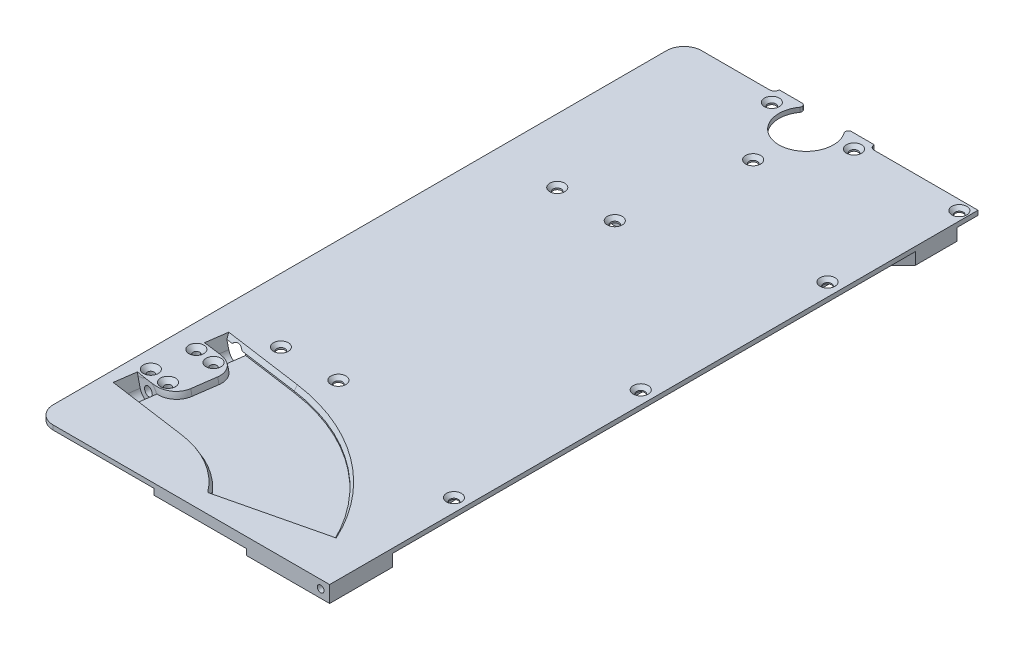
SolidWorks part; units mm, degrees
ref_plane "Front Plane" through (0, 0, 0) normal (0, 0, 1) x (1, 0, 0)
ref_plane "Top Plane" through (0, 0, 0) normal (0, 1, 0) x (1, 0, 0)
ref_plane "Right Plane" through (0, 0, 0) normal (1, 0, 0) x (0, 0, -1)
sketch "Sketch1" plane through (0, 0, 0) normal (0, 1, 0) x (1, 0, 0)
  line L0 (40, 88.1) -> (-40, -88.1) construction
  line L1 (-40, 88.1) -> (40, 88.1) construction
  line L2 (-40, 88.1) -> (-40, -88.1) construction
  line L3 (-40, -88.1) -> (40, -88.1) construction
  line L4 (40, 88.1) -> (40, -88.1) construction
  line L5 (40, 86.8) -> (-34, 86.8)
  line L6 (40, 86.8) -> (40, -86.8)
  line L7 (40, -86.8) -> (-34, -86.8)
  line L8 (-38.7, 82.1) -> (-38.7, -82.1)
  arc A0 (-34, 86.8) -> (-38.7, 82.1) centre (-34, 82.1) ccw
  arc A1 (-34, -86.8) -> (-38.7, -82.1) centre (-34, -82.1) cw
  dimension "D2" = 176.2
  dimension "D3" = 1.3
  dimension "D4" = 1.3
  dimension "D5" = 6
  dimension "D6" = 1.3
extrude "Boss-Extrude1" add sketch "Sketch1" against normal blind 1.2
sketch "Sketch4" plane through (0, -1.2, 0) normal (0, -1, 0) x (-1, 0, 0)
  line L0 (-40, -86.8) -> (-40, 86.8) construction
  line L1 (-40, -76.8) -> (22.7, -76.8)
  line L2 (-40, -76.8) -> (-40, 81.2)
  line L3 (-40, 81.2) -> (22.7, 81.2)
  line L4 (22.7, -76.8) -> (22.7, 81.2)
  line L7 (40, 88.1) -> (40, -88.1) construction
  line L8 (40, 88.1) -> (-40, 88.1) construction
  dimension "D1" = 158
  dimension "D3" = 17.3
  dimension "D2" = 6.9
extrude "Boss-Extrude3" add sketch "Sketch4" along normal blind 3.2
sketch "Sketch6" plane through (0, -1.2, 0) normal (0, -1, 0) x (1, 0, 0)
  line L0 (-40, -88.1) -> (-40, 88.1) construction
  line L1 (-22.8, -76.4) -> (-36.3, -76.4)
  line L2 (-22.8, -76.4) -> (-22.8, -64.75)
  line L3 (-22.8, -64.75) -> (-36.3, -64.75)
  line L4 (-36.3, -76.4) -> (-36.3, -64.75)
  line L5 (-22.8, 70.65) -> (-36.3, 70.65)
  line L6 (-22.8, 70.65) -> (-22.8, 41.45)
  line L7 (-22.8, 41.45) -> (-36.3, 41.45)
  line L8 (-36.3, 70.65) -> (-36.3, 41.45)
  line L9 (-40, -88.1) -> (40, -88.1) construction
  line L10 (-25.5, 56.05) -> (-22.8, 56.05) construction
  line L11 (-22.7, 76.8) -> (-22.7, -81.2) construction
  circle A0 centre (-25.5, -68.35) radius 1.1
  circle A1 centre (-25.5, 56.05) radius 1.1
  dimension "D7" = 2.2
  dimension "D1" = 3.7
  dimension "D2" = 29.2
  dimension "D3" = 17.2
  dimension "D4" = 124.4
  dimension "D5" = 19.75
  dimension "D6" = 2.8
  dimension "D8" = 2.8
  dimension "D9" = 3.6
  dimension "D10" = 5.7
extrude "Boss-Extrude4" add sketch "Sketch6" along normal blind 5.1
sketch "Sketch7" plane through (0, -1.2, 0) normal (0, -1, 0) x (1, 0, 0)
  line L0 (-22.7, 76.8) -> (-22.7, -81.2) construction
  line L1 (-22.8, -76.4) -> (-22.7, -76.4)
  line L2 (-22.8, -76.4) -> (-22.8, -64.75)
  line L3 (-22.8, -64.75) -> (-22.7, -64.75)
  line L4 (-22.7, -76.4) -> (-22.7, -64.75)
  line L5 (-22.8, -64.75) -> (-36.3, -64.75) construction
  line L6 (-22.7, 76.8) -> (-22.7, -81.2) construction
  line L7 (-22.8, 70.65) -> (-22.7, 70.65)
  line L8 (-22.8, 70.65) -> (-22.8, 41.45)
  line L9 (-22.8, 41.45) -> (-22.7, 41.45)
  line L10 (-22.7, 70.65) -> (-22.7, 41.45)
  line L11 (-36.3, 41.45) -> (-22.8, 41.45) construction
extrude "Boss-Extrude5" add sketch "Sketch7" along normal up to surface (3.2 mm away) up to face at (8.65, -4.4, -2.2)
sketch "Sketch9" plane through (0, 0, 0) normal (0, 1, 0) x (1, 0, 0)
  line L0 (-25.9598, -43.3304) -> (-31.3073, -42.5789) construction
  line L1 (-31.3073, -42.5789) -> (-34.9258, -68.3259) construction
  line L2 (-34.9258, -68.3259) -> (-29.5783, -69.0774) construction
  line L3 (-29.5783, -69.0774) -> (-25.9598, -43.3304) construction
  line L4 (-22.8, -70.65) -> (-36.3, -70.65) construction
  line L8 (-36.3, -70.65) -> (-36.3, -41.45) construction
  line L9 (-34.9258, -68.3259) -> (-34.2299, -63.3745)
  line L10 (-34.9258, -68.3259) -> (-29.5783, -69.0774)
  line L11 (-34.2299, -63.3745) -> (-28.8825, -64.1261)
  line L12 (-29.5783, -69.0774) -> (-28.8825, -64.1261)
  line L13 (-25.9598, -43.3304) -> (-31.3073, -42.5789)
  line L14 (-25.9598, -43.3304) -> (-26.6557, -48.2818)
  line L15 (-31.3073, -42.5789) -> (-32.0032, -47.5303)
  line L16 (-26.6557, -48.2818) -> (-32.0032, -47.5303)
  line L17 (-29.5783, -69.0774) -> (-22.6165, -70.0558) construction
  line L18 (-22.6165, -70.0558) -> (-22.7, -70.65) construction
  dimension "D1" = 5.4
  dimension "D3" = 8
  dimension "D2" = 26
  dimension "D4" = 1.3742
  dimension "D5" = 5
  dimension "D6" = 0.6
sketch "Sketch10" plane through (0, -6.3, 0) normal (0, -1, 0) x (1, 0, 0)
  line L0 (-25.9598, 43.3304) -> (-25.6956, 41.45)
  line L1 (-36.3, 41.45) -> (-22.8, 41.45) construction
  line L2 (-25.9598, 43.3304) -> (-39.3399, 41.45)
  line L3 (-36.3, 41.45) -> (-22.7, 41.45) construction
  line L4 (-25.9598, 43.3304) -> (-31.3073, 42.5789) construction
  line L5 (-25.9598, 43.3304) -> (-26.6557, 48.2818) construction
  line L6 (-39.3399, 41.45) -> (-25.6956, 41.45)
  line L7 (-29.5783, 69.0774) -> (-29.7994, 70.65)
  line L8 (-22.7, 70.65) -> (-36.3, 70.65) construction
  line L9 (-29.7994, 70.65) -> (-36.3, 70.65)
  line L10 (-36.3, 70.65) -> (-36.3, 68.1327)
  line L11 (-36.3, 70.65) -> (-36.3, 41.45) construction
  line L12 (-36.3, 68.1327) -> (-29.5783, 69.0774)
  line L13 (-29.5783, 69.0774) -> (-28.8825, 64.1261) construction
  line L14 (-36.3, 70.65) -> (-36.3, 41.45) construction
extrude "Cut-Extrude5" cut sketch "Sketch10" against normal up to surface (5.1 mm away) up to face at (-14.9304, -1.2, -3.7167)
extrude "Cut-Extrude6" cut sketch "Sketch9" against normal blind 5.2
sketch "Sketch11" plane through (-9.3972, 0, 66.8646) normal (-0.1392, 0, 0.9903) x (0.9903, 0, 0.1392)
  line L0 (-19.6768, 0) -> (-25.0768, 0) construction
  line L1 (-22.3768, -2.5) -> (-22.3768, 0) construction
  circle A0 centre (-22.3768, -2.5) radius 1.2
  dimension "D1" = 2.4
  dimension "D2" = 2.5
extrude "Cut-Extrude7" cut sketch "Sketch11" against normal blind 5.4
sketch "Sketch15" plane through (-9.3972, 0, 66.8646) normal (-0.1392, 0, 0.9903) x (0.9903, 0, 0.1392)
  line L0 (-22.3768, -2.5) -> (-24.9722, -3.2442) construction
  line L1 (-19.6768, -5.2) -> (-25.0768, -5.2) construction
  line L2 (-24.9722, -3.2442) -> (-25.9024, 0) construction
  line L3 (-21.5889, 0) -> (-26.8973, 0) construction
  line L4 (-25.9024, 0) -> (-25.0768, 0)
  line L5 (-25.0768, -5.2) -> (-25.0768, 0) construction
  line L6 (-25.0768, 0) -> (-25.0768, -2.8795)
  line L7 (-25.0768, -2.8795) -> (-25.9024, 0)
  circle A0 centre (-22.3768, -2.5) radius 1.2 construction
  dimension "D1" = 16
  dimension "D2" = 2.7
extrude "Cut-Extrude8" cut sketch "Sketch15" along normal up to surface (5 mm away) up to face at (-32.2521, -0.6, 68.7016)
sketch "Sketch17" plane through (-9.3972, 0, 66.8646) normal (-0.1392, 0, 0.9903) x (0.9903, 0, 0.1392)
  line L0 (-25.0768, -2.8795) -> (-24.9722, -3.2442)
  line L1 (-25.9024, 0) -> (-25.0768, -2.8795) construction
  line L2 (-19.6768, -1.2) -> (-19.6768, -6.3) construction
  line L3 (-19.6768, -2.5) -> (-19.6768, -6.3)
  line L4 (-19.6768, -6.3) -> (-25.0768, -6.3)
  line L5 (-25.0768, -6.3) -> (-25.0768, -2.8795)
  line L6 (-26.4645, -6.3) -> (-19.6768, -6.3) construction
  arc A0 (-19.6768, -2.5) -> (-24.9722, -3.2442) centre (-22.3768, -2.5) cw
extrude "Boss-Extrude6" add sketch "Sketch17" along normal up to surface (5 mm away) up to face at (-33.8587, -4.0399, 68.4758)
sketch "Sketch18" plane through (-7.1704, 0, 51.0203) normal (0.1392, 0, -0.9903) x (-0.9903, 0, -0.1392)
  line L3 (25.9024, 0) -> (25.0768, 0)
  line L4 (25.0768, 0) -> (25.0768, -2.8795)
  line L5 (25.0768, -2.8795) -> (25.9024, 0)
  line L6 (25.9024, 0) -> (25.0768, 0)
  line L7 (25.0768, 0) -> (25.0768, -2.8795)
  line L8 (25.0768, -2.8795) -> (25.9024, 0)
  dimension "D1" = 0
extrude "Cut-Extrude9" cut sketch "Sketch18" along normal up to surface (5 mm away) up to face at (-28.6336, -0.6, 42.9547)
sketch "Sketch19" plane through (-7.1704, 0, 51.0203) normal (0.1392, 0, -0.9903) x (-0.9903, 0, -0.1392)
  line L4 (25.0768, -2.8795) -> (24.9722, -3.2442)
  line L5 (19.6768, -2.5) -> (19.6768, -6.3)
  line L6 (19.6768, -6.3) -> (25.0768, -6.3)
  line L7 (25.0768, -6.3) -> (25.0768, -2.8795)
  line L8 (25.0768, -2.8795) -> (24.9722, -3.2442)
  line L9 (19.6768, -2.5) -> (19.6768, -6.3)
  line L10 (19.6768, -6.3) -> (25.0768, -6.3)
  line L11 (25.0768, -6.3) -> (25.0768, -2.8795)
  arc A1 (19.6768, -2.5) -> (24.9722, -3.2442) centre (22.3768, -2.5) ccw
  arc A2 (19.6768, -2.5) -> (24.9722, -3.2442) centre (22.3768, -2.5) ccw
  dimension "D1" = 0
extrude "Boss-Extrude7" add sketch "Sketch19" along normal up to surface (5 mm away) up to face at (-31.2741, -4.0399, 42.5836)
sketch "Sketch20" plane through (0, -6.3, 0) normal (0, -1, 0) x (1, 0, 0)
  line L0 (-36.3, 68.1327) -> (-36.3, 41.8772) construction
  line L1 (-36.3, 59.05) -> (-28.3, 59.05)
  line L2 (-36.3, 59.05) -> (-36.3, 53.05)
  line L3 (-36.3, 53.05) -> (-28.3, 53.05)
  line L4 (-28.3, 59.05) -> (-28.3, 53.05)
  line L5 (-25.5, 56.05) -> (-28.3, 56.05) construction
extrude "Cut-Extrude10" cut sketch "Sketch20" against normal blind 3.6
sketch "Sketch22" plane through (0, -2.7, 0) normal (0, -1, 0) x (-1, 0, 0)
  line L0 (28.3, -59.05) -> (36.3, -59.05) construction
  line L1 (24.0566, -58.55) -> (26.9434, -58.55)
  line L2 (26.9434, -58.55) -> (28.3868, -56.05) construction
  line L3 (28.3868, -56.05) -> (26.9434, -53.55) construction
  line L4 (26.9434, -53.55) -> (24.0566, -53.55)
  line L5 (24.0566, -53.55) -> (22.6132, -56.05)
  line L6 (22.6132, -56.05) -> (24.0566, -58.55)
  line L7 (26.9434, -58.55) -> (28.3, -58.55)
  line L8 (28.3, -53.05) -> (28.3, -59.05) construction
  line L9 (28.3, -58.55) -> (28.3, -53.55)
  line L10 (28.3, -53.55) -> (26.9434, -53.55)
  circle A0 centre (25.5, -56.05) radius 2.5 construction
  dimension "D1" = 5
extrude "Cut-Extrude12" cut sketch "Sketch22" along normal blind 1.8
ref_plane "Plane1" through (-7.1426, 0, 50.8222) normal (0.1392, 0, -0.9903) x (-0.9903, 0, -0.1392)
sketch "Sketch23" plane through (-7.1704, 0, 51.0203) normal (0.1392, 0, -0.9903) x (-0.9903, 0, -0.1392)
  circle A0 centre (22.3768, -2.5) radius 1.2
  dimension "D1" = 2.4
extrude "Cut-Extrude13" cut sketch "Sketch23" against normal blind 5.4
sketch "Sketch24" plane through (0, 0, 0) normal (0, 1, 0) x (1, 0, 0)
  line L0 (-32.365, -50.1049) -> (-27.0176, -50.8565) construction
  line L1 (-32.365, -50.1049) -> (-33.8681, -60.7998) construction
  line L2 (-27.0176, -50.8565) -> (-28.5206, -61.5514) construction
  line L3 (-33.8681, -60.7998) -> (-28.5206, -61.5514) construction
  line L5 (-32.1249, -42.464) -> (-32.8208, -47.4153) construction
  line L6 (-29.3294, -47.906) -> (-29.6913, -50.4807) construction
  line L7 (-32.8208, -47.4153) -> (-26.6557, -48.2818) construction
  line L8 (-28.8825, -64.1261) -> (-35.0476, -63.2596) construction
  line L9 (-28.1411, -48.073) -> (-30.5178, -47.739) construction
  circle A0 centre (-32.365, -50.1049) radius 2 construction
  circle A1 centre (-27.0176, -50.8565) radius 2 construction
  circle A2 centre (-28.5206, -61.5514) radius 2 construction
  circle A3 centre (-33.8681, -60.7998) radius 2 construction
  circle A4 centre (-32.365, -50.1049) radius 0.9
  circle A5 centre (-27.0176, -50.8565) radius 0.9
  circle A6 centre (-28.5206, -61.5514) radius 0.9
  circle A7 centre (-33.8681, -60.7998) radius 0.9
  dimension "D1" = 4
  dimension "D2" = 1.8
  dimension "D3" = 5.4
  dimension "D4" = 2.6
  dimension "D5" = 2.6
extrude "Cut-Extrude14" cut sketch "Sketch24" against normal through all
chamfer "Chamfer1" distance 1.1 angle 45 4 edges at (-33.8681, 0, 61.6998) (-28.5206, 0, 62.4514) (-32.365, 0, 51.0049) (-27.0176, 0, 51.7565)
sketch "Sketch26" plane through (-6.4746, 0, 46.0689) normal (0.1392, 0, -0.9903) x (-0.9903, 0, -0.1392)
  circle A0 centre (22.3768, -2.5) radius 2
  circle A1 centre (22.3768, -2.5) radius 1.2 construction
  dimension "D1" = 4
extrude "Cut-Extrude15" cut sketch "Sketch26" along normal blind 12
sketch "Sketch27" plane through (-10.0931, 0, 71.8159) normal (-0.1392, 0, 0.9903) x (0.9903, 0, 0.1392)
  circle A0 centre (-22.3768, -2.5) radius 2
  dimension "D1" = 4
extrude "Cut-Extrude16" cut sketch "Sketch27" along normal blind 12
sketch "Sketch28" plane through (0, -6.3, 0) normal (0, -1, 0) x (1, 0, 0)
  line L1 (-28.3868, -68.35) -> (-26.9434, -70.85) construction
  line L2 (-26.9434, -70.85) -> (-24.0566, -70.85)
  line L3 (-24.0566, -70.85) -> (-22.6132, -68.35)
  line L4 (-22.6132, -68.35) -> (-24.0566, -65.85)
  line L5 (-24.0566, -65.85) -> (-26.9434, -65.85)
  line L6 (-26.9434, -65.85) -> (-28.3868, -68.35) construction
  line L8 (-22.8, -64.75) -> (-36.3, -64.75) construction
  line L10 (-26.9434, -70.85) -> (-35.1868, -70.85)
  line L11 (-35.1868, -70.85) -> (-35.1868, -64.75)
  line L12 (-35.1868, -64.75) -> (-28.3868, -64.75)
  line L14 (-28.3868, -64.75) -> (-28.3868, -65.85)
  line L15 (-28.3868, -65.85) -> (-26.9434, -65.85)
  circle A0 centre (-25.5, -68.35) radius 2.5 construction
  circle A1 centre (-25.5, -68.35) radius 1.1 construction
  dimension "D1" = 5
  dimension "D2" = 6.8
extrude "Cut-Extrude17" cut sketch "Sketch28" along normal blind 1.8 from surface at -3.6 starting at face at (-29.4232, -2.7, 55.9978)
sketch "Sketch29" plane through (0, -6.3, 0) normal (0, -1, 0) x (1, 0, 0)
  line L0 (-22.8, -64.75) -> (-36.3, -64.75) construction
  line L1 (-35.1868, -70.85) -> (-28.3868, -70.85)
  line L2 (-35.1868, -70.85) -> (-35.1868, -64.75)
  line L3 (-35.1868, -64.75) -> (-28.3868, -64.75)
  line L4 (-28.3868, -70.85) -> (-28.3868, -64.75)
extrude "Cut-Extrude18" cut sketch "Sketch29" against normal up to next
sketch "Sketch31" plane through (0, -4.4, 0) normal (0, -1, 0) x (1, 0, 0)
  line L0 (40, 70) -> (32.8, 62.8)
  line L1 (40, -81.2) -> (40, 76.8) construction
  line L2 (32.8, 62.8) -> (32.8, -62.8)
  line L3 (32.8, -62.8) -> (40, -70)
  line L4 (40, -70) -> (40, 70)
  line L5 (40, -88.1) -> (40, 88.1) construction
  point P8 (40, 0)
  dimension "D1" = 140
  dimension "D2" = 45
  dimension "D3" = 45
  dimension "D4" = 7.2
extrude "Cut-Extrude19" cut sketch "Sketch31" against normal up to surface (3.2 mm away) up to face at (-25.5, -1.2, 54.95)
sketch "Sketch32" plane through (0, 0, 0) normal (0, 1, 0) x (1, 0, 0)
  line L0 (36.5, 50) -> (36.5, 0) construction
  line L1 (36.5, 0) -> (36.5, -50) construction
  line L2 (40, 86.8) -> (40, -86.8) construction
  line L3 (36.5, 0) -> (40, 0) construction
  line L5 (40, -70) -> (40, 70) construction
  circle A0 centre (36.5, 50) radius 1.1
  circle A1 centre (36.5, 0) radius 1.1
  circle A2 centre (36.5, -50) radius 1.1
  dimension "D1" = 2.2
  dimension "D2" = 50
  dimension "D3" = 3.5
extrude "Cut-Extrude20" cut sketch "Sketch32" against normal up to next
chamfer "Chamfer2" distance 0.9 angle 45 3 edges at (36.5, 0, 51.1) (36.5, 0, 1.1) (36.5, 0, -48.9)
sketch "Sketch33" plane through (0, 0, 0) normal (0, 1, 0) x (1, 0, 0)
  line L0 (-28.6614, -43.1527) -> (-10.8019, -45.6627) construction
  line L1 (-28.6614, -43.1527) -> (-29.3016, -47.708) construction
  line L2 (-29.3016, -47.708) -> (-26.8259, -48.0559) construction
  line L3 (-22.5704, -53.7031) -> (-23.4612, -60.0408) construction
  line L4 (-29.1084, -64.2963) -> (-31.584, -63.9484) construction
  line L5 (-31.584, -63.9484) -> (-32.2242, -68.5036) construction
  line L6 (-32.2242, -68.5036) -> (-14.3647, -71.0136) construction
  line L7 (-25.9598, -43.3304) -> (-26.6557, -48.2818) construction
  line L8 (-28.1411, -48.073) -> (-30.5178, -47.739) construction
  line L9 (-32.8208, -47.4153) -> (-26.6557, -48.2818) construction
  line L10 (28.8162, -74.5036) -> (2.6914, -80.7659) construction
  line L11 (2.6914, -80.7659) -> (9.7561, -89.6538) construction
  line L14 (28.8162, -74.5036) -> (9.7561, -89.6538) construction
  line L15 (-29.0805, -64.0982) -> (-31.7543, -63.7225)
  line L16 (-31.7543, -63.7225) -> (-32.4501, -68.6738)
  line L17 (-32.4501, -68.6738) -> (-14.3926, -71.2116)
  line L18 (29.1042, -74.6402) -> (2.6138, -80.9902)
  line L19 (-28.8316, -42.9268) -> (-10.7741, -45.4647)
  line L20 (-28.8316, -42.9268) -> (-29.5275, -47.8782)
  line L21 (-29.5275, -47.8782) -> (-26.8538, -48.254)
  line L22 (-22.7685, -53.6753) -> (-23.6592, -60.013)
  arc A0 (-26.8259, -48.0559) -> (-22.5704, -53.7031) centre (-27.5218, -53.0072) cw construction
  arc A1 (-23.4612, -60.0408) -> (-29.1084, -64.2963) centre (-28.4125, -59.345) cw construction
  arc A2 (-14.3647, -71.0136) -> (2.6914, -80.7659) centre (-18.0527, -97.2547) cw construction
  arc A3 (-10.8019, -45.6627) -> (28.8162, -74.5036) centre (-18.0527, -97.2547) cw construction
  arc A4 (-14.3926, -71.2116) -> (2.6138, -80.9902) centre (-18.0527, -97.2547) cw
  arc A5 (-10.7741, -45.4647) -> (29.1042, -74.6402) centre (-18.0527, -97.2547) cw
  arc A6 (-26.8538, -48.254) -> (-22.7685, -53.6753) centre (-27.5218, -53.0072) cw
  arc A7 (-23.6592, -60.013) -> (-29.0805, -64.0982) centre (-28.4125, -59.345) cw
  point P17 (-29.3294, -47.906)
  dimension "D2" = 2.5
  dimension "D3" = 5
  dimension "D7" = 26.499
  dimension "D1" = 4.6
  dimension "D4" = 16.4
  dimension "D5" = 0.2
  dimension "D6" = 18.035
  dimension "D8" = 65
  dimension "D9" = 21.48
sketch "Sketch34" plane through (0, -1.2, 0) normal (0, -1, 0) x (-1, 0, 0)
  line L0 (-40, -76.8) -> (22.7, -76.8) construction
  line L1 (-40, -86.8) -> (7.06, -86.8)
  line L2 (-40, -86.8) -> (-40, -76.8)
  line L3 (-40, -76.8) -> (7.06, -76.8)
  line L4 (7.06, -86.8) -> (7.06, -76.8)
  line L6 (40, 88.1) -> (-40, 88.1) construction
  line L7 (7.16, -76.8) -> (16.16, -67.8) construction
  line L8 (16.16, -67.8) -> (16.16, 88.1) construction
  line L9 (40, 88.1) -> (40, -88.1) construction
  line L10 (40, -88.1) -> (-40, -88.1) construction
  dimension "D2" = 23.84
  dimension "D3" = 11.3
  dimension "D1" = 135
  dimension "D4" = 9
extrude "Boss-Extrude8" add sketch "Sketch34" along normal blind 1.6
sketch "Sketch35" plane through (0, -2.8, 0) normal (0, -1, 0) x (1, 0, 0)
  line L0 (40, 76.8) -> (-22.7, 76.8) construction
  line L1 (40, 86.8) -> (17.8, 86.8)
  line L2 (40, 86.8) -> (40, 76.8)
  line L3 (40, 76.8) -> (17.8, 76.8)
  line L4 (17.8, 86.8) -> (17.8, 76.8)
  line L5 (-40, -88.1) -> (-40, 88.1) construction
  dimension "D1" = 57.8
extrude "Boss-Extrude9" add sketch "Sketch35" along normal up to surface (1.6 mm away) up to face at (-6.283, -4.4, -4.7182)
extrude "Cut-Extrude21" cut sketch "Sketch33" against normal blind 1.6
sketch "Sketch37" plane through (-9.3972, 0, 66.8646) normal (-0.1392, 0, 0.9903) x (0.9903, 0, 0.1392)
  line L5 (-21.4768, 0) -> (-19.8768, 0) construction
  line L6 (-19.8768, 0) -> (-19.8768, -1.6)
  line L7 (-19.8768, 0) -> (-25.9024, 0) construction
  line L8 (-21.4768, 0) -> (-21.4768, 1)
  line L9 (-21.4768, 1) -> (-19.8768, 1)
  line L10 (-19.8768, 1) -> (-19.8768, 0)
  arc A1 (-21.4768, 0) -> (-19.8768, -1.6) centre (-22.3768, -2.5) cw
  circle A2 centre (-22.3768, -2.5) radius 1.2 construction
  dimension "D1" = 1
sketch "Sketch44" plane through (0, 0, 86.8) normal (0, 0, 1) x (1, 0, 0)
  line L0 (40, -4.4) -> (40, 0) construction
  line L1 (17.8, -4.4) -> (40, -4.4) construction
  circle A0 centre (37.6, -2.2) radius 0.9
  dimension "D1" = 1.8
extrude "Cut-Extrude22" cut sketch "Sketch44" against normal blind 9
sketch "Sketch45" plane through (0, 0, 0) normal (0, 1, 0) x (1, 0, 0)
  line L0 (-40, 88.1) -> (40, 88.1) construction
  line L1 (40, 86.8) -> (40, -86.8) construction
  circle A0 centre (37.6, 84.2) radius 1.1
  dimension "D3" = 2.2
  dimension "D1" = 3.9
extrude "Cut-Extrude23" cut sketch "Sketch45" against normal up to next
chamfer "Chamfer3" distance 0.9 angle 45 1 edges at (37.6, 0, -83.1)
sketch "Sketch50" plane through (-9.3972, 0, 66.8646) normal (-0.1392, 0, 0.9903) x (0.9903, 0, 0.1392)
  line L5 (-23.931, -0.3449) -> (-25.469, -0.7859)
  line L6 (-25.9024, 0) -> (-24.9722, -3.2442) construction
  arc A2 (-19.8768, -1.6) -> (-23.931, -0.3449) centre (-22.3768, -2.5) ccw
  circle A3 centre (-22.3768, -2.5) radius 1.2 construction
  arc A4 (-19.8768, 0) -> (-25.469, -0.7859) centre (-22.3768, -2.5) ccw
sketch "Sketch51" plane through (0, -1.6, 0) normal (0, 1, 0) x (1, 0, 0)
  line L0 (-29.0805, -64.0982) -> (-29.7764, -69.0496)
  line L1 (-29.7764, -69.0496) -> (-20.0718, -70.4135)
  line L2 (-20.0718, -70.4135) -> (-16.4533, -44.6665)
  line L3 (-16.4533, -44.6665) -> (-26.1579, -43.3026)
  line L4 (-26.1579, -43.3026) -> (-26.8538, -48.254)
  line L5 (-29.5783, -69.0774) -> (-28.8825, -64.1261) construction
  line L6 (-22.7685, -53.6753) -> (-23.6592, -60.013)
  line L7 (-29.0805, -64.0982) -> (-31.5562, -63.7503) construction
  arc A0 (-29.0805, -64.0982) -> (-23.6592, -60.013) centre (-28.4125, -59.345) ccw
  arc A1 (-26.8538, -48.254) -> (-22.7685, -53.6753) centre (-27.5218, -53.0072) cw
  dimension "D2" = 4.8
  dimension "D1" = 5
  dimension "D3" = 5
ref_plane "Plane3" through (-21.9881, -6.367, -3.0902) normal (0.9519, 0.2756, 0.1338) x (0.1285, 0.0372, -0.991)
sketch "Sketch54" plane through (-7.1704, 0, 51.0203) normal (0.1392, 0, -0.9903) x (-0.9903, 0, -0.1392)
  line L0 (24.9722, -3.2442) -> (25.9024, 0) construction
  arc A0 (19.8768, -1.6) -> (23.931, -0.3449) centre (22.3768, -2.5) cw
  dimension "D1" = 1.8
sketch "Sketch53" plane through (-21.9881, -6.367, -3.0902) normal (0.9519, 0.2756, 0.1338) x (0.1285, 0.0372, -0.991)
  line L0 (-67.2286, 8.8737) -> (-72.2248, 9.0673)
  line L2 (-72.2248, 9.0673) -> (-71.8455, 18.8599)
  line L3 (-71.8455, 18.8599) -> (-45.8649, 17.8535)
  line L4 (-45.8649, 17.8535) -> (-46.2443, 8.0608)
  line L6 (-46.2443, 8.0608) -> (-51.2406, 8.2544)
  line L7 (-62.2464, 13.4843) -> (-55.8511, 13.2366)
  line L8 (-67.3185, 6.5515) -> (-72.3148, 6.7451) construction
  line L11 (-46.3343, 5.7386) -> (-51.3305, 5.9322) construction
  line L12 (-67.2286, 8.8737) -> (-67.3065, 6.8613) construction
  arc A0 (-67.2286, 8.8737) -> (-62.2464, 13.4843) centre (-62.4322, 8.6879) cw
  arc A1 (-51.2406, 8.2544) -> (-55.8511, 13.2366) centre (-56.037, 8.4402) ccw
  dimension "D1" = 4.8
  dimension "D2" = 5
sweep "Cut-Sweep2" cut profiles "Sketch51" path "Sketch54"
extrude "Cut-Extrude24" cut sketch "Sketch53" against normal blind 1.8
chamfer "Chamfer4" distance 1.2 angle 30 5 edges at (-4.9435, 0, 74.4559) (15.859, 0, 77.8152) (12.8279, 0, 55.046)
sketch "Sketch55" plane through (0, -4.4, 0) normal (0, -1, 0) x (1, 0, 0)
  line L0 (-25.6956, 41.45) -> (-22.8, 41.45) construction
  line L1 (-3, 41.45) -> (-38.8, 41.45) construction
  line L2 (-3, 41.45) -> (-3, -38.95) construction
  line L3 (-3, -38.95) -> (-38.8, -38.95) construction
  line L4 (-38.8, 41.45) -> (-38.8, -38.95) construction
  line L6 (-3, 38.25) -> (-3, -35.75)
  line L7 (-6.2, -38.95) -> (-38.8, -38.95)
  line L8 (-38.8, -38.95) -> (-38.8, 41.45)
  line L9 (-38.8, 41.45) -> (-6.2, 41.45)
  line L11 (-40, -88.1) -> (-40, 88.1) construction
  arc A0 (-6.2, 41.45) -> (-3, 38.25) centre (-6.2, 38.25) cw
  arc A1 (-3, -35.75) -> (-6.2, -38.95) centre (-6.2, -35.75) cw
  dimension "D4" = 3.2
  dimension "D1" = 80.4
  dimension "D2" = 35.8
  dimension "D3" = 1.2
extrude "Cut-Extrude25" cut sketch "Sketch55" along direction (0, -1, 0) on the side against the normal offset from surface (4 mm away) 0.4
sketch "Sketch56" plane through (0, -0.4, 0) normal (0, -1, 0) x (1, 0, 0)
  line L0 (-3, 35.95) -> (-21.6, 35.95)
  line L1 (-3, -33.45) -> (-21.6, -33.45)
  line L2 (-3, 38.25) -> (-3, -35.75) construction
  line L3 (-23.9, -35.75) -> (-23.9, -38.95)
  line L4 (-6.2, -38.95) -> (-38.7, -38.95) construction
  line L5 (-21.6, -35.75) -> (-6.2, -35.75) construction
  line L6 (-3, -33.45) -> (-3, -35.75)
  line L7 (-6.2, -38.95) -> (-23.9, -38.95)
  line L8 (-23.9, 38.25) -> (-23.9, 41.45)
  line L9 (-38.7, 41.45) -> (-6.2, 41.45) construction
  line L10 (-23.9, 41.45) -> (-6.2, 41.45)
  line L11 (-3, 35.95) -> (-3, 38.25)
  arc A0 (-21.6, -33.45) -> (-23.9, -35.75) centre (-21.6, -35.75) ccw
  arc A1 (-21.6, 35.95) -> (-23.9, 38.25) centre (-21.6, 38.25) cw
  circle A2 centre (-21.6, -35.75) radius 1.1 construction
  circle A4 centre (-6.2, -35.75) radius 1.1 construction
  arc A5 (-6.2, -38.95) -> (-3, -35.75) centre (-6.2, -35.75) ccw construction
  arc A6 (-3, -35.75) -> (-6.2, -38.95) centre (-6.2, -35.75) cw
  arc A7 (-6.2, 41.45) -> (-3, 38.25) centre (-6.2, 38.25) cw
  dimension "D1" = 2.2
  dimension "D3" = 15.4
extrude "Boss-Extrude10" add sketch "Sketch56" along normal blind 0.9
sketch "Sketch57" plane through (0, -1.3, 0) normal (0, -1, 0) x (-1, 0, 0)
  circle A0 centre (21.6, 35.75) radius 1.1
  circle A1 centre (6.2, 35.75) radius 1.1
  circle A2 centre (6.2, -38.25) radius 1.1
  circle A3 centre (21.6, -38.25) radius 1.1
  arc A4 (23.9, -38.25) -> (21.6, -35.95) centre (21.6, -38.25) ccw construction
  arc A5 (3, -38.25) -> (6.2, -41.45) centre (6.2, -38.25) ccw construction
  arc A8 (6.2, 38.95) -> (3, 35.75) centre (6.2, 35.75) ccw construction
  arc A9 (21.6, 33.45) -> (23.9, 35.75) centre (21.6, 35.75) ccw construction
  dimension "D1" = 2.2
extrude "Cut-Extrude26" cut sketch "Sketch57" against normal up to surface (1.3 mm away) up to face at (37.6, 0, -86.2)
sketch "Sketch58" plane through (0, -1.3, 0) normal (0, -1, 0) x (1, 0, 0)
  line L0 (-22.7, -38.95) -> (-22.7, -37.7699)
  line L1 (-23.9, -35.75) -> (-23.9, -38.95)
  line L2 (-23.9, -35.75) -> (-23.9, -38.95) construction
  line L3 (-23.9, -38.95) -> (-22.7, -38.95)
  arc A0 (-23.9, -35.75) -> (-22.7, -37.7699) centre (-21.6, -35.75) ccw
  arc A1 (-21.6, -33.45) -> (-23.9, -35.75) centre (-21.6, -35.75) ccw construction
extrude "Cut-Extrude27" cut sketch "Sketch58" against normal up to surface (0.9 mm away) up to face at (-22.3153, -0.4, 1.25)
chamfer "Chamfer5" distance 0.9 angle 45 4 edges at (-21.6, 0, 37.15) (-6.2, 0, 37.15) (-6.2, 0, -36.85) (-21.6, 0, -36.85)
sketch "Sketch59" plane through (0, -4.4, 0) normal (0, -1, 0) x (1, 0, 0)
  line L0 (32.8, -62.8) -> (32.8, 62.8) construction
  line L1 (32.8, 33.8) -> (-3, 33.8)
  line L2 (32.8, 33.8) -> (32.8, 17.9)
  line L3 (32.8, 17.9) -> (-3, 17.9)
  line L4 (-3, 33.8) -> (-3, 17.9)
  line L5 (-3, 35.95) -> (-3, -33.45) construction
  line L6 (32.8, 25.85) -> (-3, 25.85) construction
  line L7 (-6.2, 41.45) -> (-22.8, 41.45) construction
  dimension "D1" = 15.6
  dimension "D2" = 15.9
extrude "Cut-Extrude28" cut sketch "Sketch59" against normal blind 0.4
sketch "Sketch60" plane through (0, -4, 0) normal (0, -1, 0) x (1, 0, 0)
  line L0 (-3, 17.9) -> (32.8, 17.9) construction
  line L1 (-3, 33.8) -> (-1.8, 33.8)
  line L2 (-3, 33.8) -> (-3, 17.9)
  line L3 (-3, 17.9) -> (-1.8, 17.9)
  line L4 (-1.8, 33.8) -> (-1.8, 17.9)
  dimension "D1" = 1.2
extrude "Cut-Extrude29" cut sketch "Sketch60" against normal up to surface (3.6 mm away) up to face at (-22.1955, -0.4, 1.0431)
fillet "Fillet1" radius 1.2 2 edges at (-1.8, -4, 25.85) (-1.8, -0.4, 25.85)
sketch "Sketch61" plane through (0, -4.4, 0) normal (0, -1, 0) x (1, 0, 0)
  line L0 (-40, -88.1) -> (-40, 88.1) construction
  line L1 (12.2, -65.4) -> (-15.8, -65.4) construction
  line L2 (12.2, -65.4) -> (12.2, -87.4) construction
  line L3 (12.2, -87.4) -> (-15.8, -87.4) construction
  line L4 (-15.8, -65.4) -> (-15.8, -87.4) construction
  line L5 (-40, -88.1) -> (40, -88.1) construction
  line L7 (-16, -86.8) -> (-16, -68.6)
  line L9 (-12.6, -65.2) -> (9, -65.2)
  line L10 (12.4, -68.6) -> (12.4, -86.8)
  line L11 (40, -86.8) -> (-34, -86.8) construction
  line L12 (-16, -86.8) -> (12.4, -86.8)
  arc A0 (-12.6, -65.2) -> (-16, -68.6) centre (-12.6, -68.6) ccw
  arc A1 (9, -65.2) -> (12.4, -68.6) centre (9, -68.6) cw
  dimension "D5" = 0.2
  dimension "D8" = 3.4
  dimension "D1" = 22
  dimension "D2" = 28
  dimension "D3" = 0.7
  dimension "D6" = 0.2
  dimension "D7" = 0.2
  dimension "D4" = 24
extrude "Cut-Extrude30" cut sketch "Sketch61" against normal up to surface (3.2 mm away) up to face at (-26.4178, -1.2, 42.3492)
sketch "Sketch62" plane through (0, -1.2, 0) normal (0, -1, 0) x (1, 0, 0)
  line L1 (12.2, -87.4) -> (-15.8, -87.4) construction
  line L2 (12.2, -87.4) -> (12.2, -65.4) construction
  line L3 (12.2, -65.4) -> (-15.8, -65.4) construction
  line L4 (-15.8, -87.4) -> (-15.8, -65.4) construction
  line L5 (-16, -68.6) -> (-16, -81.2) construction
  line L6 (-4.1, -65.2) -> (-4.1, -68.4)
  line L7 (-12.6, -65.2) -> (9, -65.2) construction
  line L8 (0.5, -65.2) -> (0.5, -68.4)
  line L9 (0.5, -65.2) -> (-4.1, -65.2)
  circle A0 centre (-12.6, -84.2) radius 1.1 construction
  circle A1 centre (9.2, -84.4) radius 1.1 construction
  circle A2 centre (-1.8, -68.4) radius 1.1 construction
  arc A3 (0.5, -68.4) -> (-4.1, -68.4) centre (-1.8, -68.4) cw
  circle A4 centre (9.2, -84.4) radius 2.3
  circle A5 centre (-12.6, -84.2) radius 2.3
  dimension "D1" = 2.2
  dimension "D2" = 28
  dimension "D3" = 22
  dimension "D4" = 0.2
  dimension "D5" = 3.2
  dimension "D6" = 3.2
  dimension "D9" = 14
  dimension "D10" = 3
  dimension "D11" = 1.2
  dimension "D12" = 1.2
extrude "Boss-Extrude11" add sketch "Sketch62" along normal blind 0.1
sketch "Sketch63" plane through (0, -1.3, 0) normal (0, -1, 0) x (1, 0, 0)
  circle A0 centre (-1.8, -68.4) radius 1.1
  circle A1 centre (9.2, -84.4) radius 1.1
  circle A2 centre (-12.6, -84.2) radius 1.1
  dimension "D1" = 2.2
extrude "Cut-Extrude31" cut sketch "Sketch63" against normal up to surface (1.3 mm away) up to face at (-21.6, 0, 36.25)
chamfer "Chamfer6" distance 0.9 angle 45 3 edges at (-12.6, 0, -85.3) (-1.8, 0, -69.5) (9.2, 0, -85.5)
sketch "Sketch64" plane through (0, -1.2, 0) normal (0, -1, 0) x (1, 0, 0)
  line L0 (-40, -88.1) -> (40, -88.1) construction
  line L1 (40, -86.8) -> (-34, -86.8) construction
  line L2 (10.9, -88.1) -> (-14.5, -88.1)
  line L3 (12.2, -86.8) -> (-15.8, -86.8)
  line L4 (12.2, -65.4) -> (12.2, -87.4) construction
  line L5 (-16, -86.8) -> (12.4, -86.8) construction
  line L6 (-15.8, -65.4) -> (-15.8, -87.4) construction
  arc A0 (12.2, -86.8) -> (10.9, -88.1) centre (12.2, -88.1) ccw
  arc A1 (-15.8, -86.8) -> (-14.5, -88.1) centre (-15.8, -88.1) cw
extrude "Boss-Extrude12" add sketch "Sketch64" against normal up to surface (1.2 mm away) up to face at (-12.6, 0, -86.2)
sketch "Sketch65" plane through (0, -1.2, 0) normal (0, -1, 0) x (1, 0, 0)
  line L2 (-15.8, -87.4) -> (-15.8, -65.4) construction
  line L3 (-40, -88.1) -> (40, -88.1) construction
  line L4 (-8.397, -88.1) -> (4.797, -88.1)
  arc A1 (4.1454, -86.8358) -> (-7.7454, -86.8358) centre (-1.8, -82.6) ccw
  arc A2 (4.1454, -86.8358) -> (4.797, -88.1) centre (4.797, -87.3) ccw
  arc A3 (-7.7454, -86.8358) -> (-8.397, -88.1) centre (-8.397, -87.3) cw
  dimension "D1" = 7.3
  dimension "D4" = 0.8
  dimension "D2" = 14
  dimension "D3" = 5.5
extrude "Cut-Extrude32" cut sketch "Sketch65" against normal up to next
sketch "Sketch66" plane through (0, -4.4, 0) normal (0, -1, 0) x (1, 0, 0)
  line L0 (-10.15, -38.95) -> (-10.15, -65.2)
  line L1 (-22.7, -38.95) -> (-6.2, -38.95) construction
  line L3 (-13.05, -38.95) -> (-13.05, -65.2299)
  line L4 (-22.7, -38.95) -> (-6.2, -38.95) construction
  line L5 (-10.15, -65.2) -> (-13.05, -65.2) construction
  line L7 (9, -65.2) -> (-12.6, -65.2) construction
  line L8 (-16, -68.6) -> (-16, -81.2) construction
  line L9 (-13.05, -38.95) -> (-10.15, -38.95)
  line L10 (-12.6, -65.2) -> (-10.15, -65.2)
  arc A0 (-12.6, -65.2) -> (-13.05, -65.2299) centre (-12.6, -68.6) ccw
  arc A1 (-12.6, -65.2) -> (-16, -68.6) centre (-12.6, -68.6) ccw construction
  point P27 (-11.6, -65.2)
  dimension "D1" = 2.9
  dimension "D2" = 4.4
extrude "Cut-Extrude33" cut sketch "Sketch66" against normal up to surface (3.1 mm away) up to face at (-6.2, -1.3, -36.85)
sketch "Sketch67" plane through (0, -4.4, 0) normal (0, -1, 0) x (1, 0, 0)
  line L0 (-3, 17.9) -> (-3, -33.45) construction
  line L1 (-3, 3.4) -> (-0.6, 3.4)
  line L2 (-3, 3.4) -> (-3, 0.5)
  line L3 (-3, 0.5) -> (-0.6, 0.5)
  line L4 (-0.6, 3.4) -> (-0.6, 0.5)
  line L5 (-10.15, -38.95) -> (-6.2, -38.95) construction
  point P6 (-3, 1.95)
  dimension "D1" = 2.4
  dimension "D3" = 40.9
extrude "Cut-Extrude34" cut sketch "Sketch67" against normal up to surface (4 mm away) up to face at (-18.9963, -0.4, 5.1776)
fillet "Fillet2" radius 1.2 1 edges at (-0.6, -0.4, 1.95)
sketch "Sketch68" plane through (0, -4.5, 0) normal (0, 1, 0) x (1, 0, 0)
  line L0 (-28.3868, 70.85) -> (-24.0566, 70.85) construction
  line L1 (-26.6, -53.55) -> (-24.4, -53.55)
  line L2 (-26.6, -53.55) -> (-26.6, -58.55)
  line L3 (-26.6, -58.55) -> (-24.4, -58.55)
  line L4 (-24.4, -53.55) -> (-24.4, -58.55)
  line L5 (-26.6, 70.85) -> (-24.4, 70.85)
  line L6 (-26.6, 70.85) -> (-26.6, 65.85)
  line L7 (-26.6, 65.85) -> (-24.4, 65.85)
  line L8 (-24.4, 70.85) -> (-24.4, 65.85)
  circle A0 centre (-25.5, 68.35) radius 1.1 construction
  circle A1 centre (-25.5, 68.35) radius 1.1 construction
  circle A2 centre (-25.5, -56.05) radius 1.1 construction
extrude "Cut-Extrude35" cut sketch "Sketch68" against normal blind 0.2
sketch "Sketch69" plane through (0, -4.7, 0) normal (0, 1, 0) x (1, 0, 0)
  line L0 (-24.4, 68.35) -> (-24.4, 70.85) construction
  line L1 (-24.4, -54.95) -> (-26.6, -54.95)
  line L2 (-24.4, -54.95) -> (-24.4, -57.15)
  line L3 (-24.4, -57.15) -> (-26.6, -57.15)
  line L4 (-26.6, -54.95) -> (-26.6, -57.15)
  line L5 (-24.4, 69.45) -> (-26.6, 69.45)
  line L6 (-24.4, 69.45) -> (-24.4, 67.25)
  line L7 (-24.4, 67.25) -> (-26.6, 67.25)
  line L8 (-26.6, 69.45) -> (-26.6, 67.25)
  line L9 (-26.6, 70.85) -> (-26.6, 65.85) construction
  line L10 (-26.6, -53.55) -> (-26.6, -58.55) construction
  line L11 (-24.4, -58.55) -> (-24.4, -53.55) construction
  arc A0 (-26.6, 68.35) -> (-24.4, 68.35) centre (-25.5, 68.35) ccw construction
  arc A1 (-24.4, 68.35) -> (-26.6, 68.35) centre (-25.5, 68.35) ccw construction
  circle A2 centre (-25.5, -56.05) radius 1.1 construction
extrude "Cut-Extrude36" cut sketch "Sketch69" against normal blind 0.2
equation "\"LCD_Height\"= 158mm"
equation "\"LCD_Width\"= 268mm"
equation "\"LCD_PCB_Height\"= 10mm"
equation "\"LCD_PCB_Width\"= 189"
equation "\"LCD_PCB_LOff\"= 38.5"
equation "\"LCD_Thick\"= 2.9mm"
equation "\"LCD_TBezel\"= 4.6mm"
equation "\"LCD_LBezel\"= 4.94mm"
equation "\"LCD_RBezel\"= 6.94mm"
equation "\"LCD_BBezel\"= 9.4mm"
equation "\"Wing_Height\"= 11.5mm"
equation "\"Wing_Width\"= 5mm"
equation "\"Wing_Corner\"= 1mm"
equation "\"Wing_Hole_VOff\"= 3.5mm"
equation "\"Wing_Hole_HOff\"= 2.8mm"
equation "\"Wing_Spacing\"= 128.9 + 2 * \"Wing_Hole_VOff\" - \"Wing_Height\""
equation "\"Wing_TOff\"= 8.35 - \"Wing_Hole_VOff\""
equation "\"Wing_DOff\"= 0.7mm"
equation "\"Wing_Thick\"= 0.3mm"
equation "\"Print_Gap\"= 0.2mm"
equation "\"Pin1_Pos\"= 89.75mm"
equation "\"Pin_Space\"= 0.5mm"
equation "\"Pin_num\"= 30"
equation "\"Min_Thick\"= 1.2mm"
equation "\"Nut_Width\"= 4.8mm"
equation "\"Nut_Height\"= 5.6mm"
equation "\"Nut_Thick\"= 1.6mm"
equation "\"Screw_Hole\"= 2.2mm"
equation "\"Screw_Chamf\"= 0.9mm"
equation "\"Bezel_Gap\"= 0.4mm"
equation "\"USB_Width\"= 16mm"
equation "\"Corner_Radius\"= 6mm"
equation "\"D2@Sketch1\"=\"LCD_Height\" + \"LCD_PCB_Height\" + \"Print_Gap\" + 2 * \"Min_Thick\" + \"Nut_Height\""
equation "\"D3@Sketch1\"=\"Print_Gap\" / 2 + \"Min_Thick\""
equation "\"D4@Sketch1\"=\"Min_Thick\" + \"Print_Gap\" / 2"
equation "\"D5@Sketch1\"=\"Corner_Radius\""
equation "\"D1@Boss-Extrude1\"=\"Min_Thick\""
equation "\"D6@Sketch1\"=\"Print_Gap\" / 2 + \"Min_Thick\""
equation "\"D1@Sketch4\"=\"LCD_Height\""
equation "\"D1@Boss-Extrude3\"=8 - \"Min_Thick\" - 0.6 - \"Print_Gap\" / 2 - \"LCD_Thick\""
equation "\"D3@Sketch4\"=\"Min_Thick\" + \"Print_Gap\" / 2 + \"USB_Width\""
equation "\"D1@Sketch6\"=3 * \"Min_Thick\" + \"Print_Gap\" / 2"
equation "\"D2@Sketch6\"=\"Nut_Width\" + 2 * \"Min_Thick\" + 22"
equation "\"D3@Sketch6\"= \"Min_Thick\" + \"USB_Width\""
equation "\"D4@Sketch6\"=\"Wing_Spacing\""
equation "\"D5@Sketch6\"=\"Min_Thick\" + \"Nut_Height\" + \"Print_Gap\"/2 + \"Wing_TOff\" + \"Wing_Height\" - \"Wing_Hole_VOff\""
equation "\"D6@Sketch6\"=\"Wing_Hole_HOff\""
equation "\"D7@Sketch6\"=\"Screw_Hole\""
equation "\"D8@Sketch6\"=\"Wing_Hole_HOff\""
equation "\"D9@Sketch6\"=\"Nut_Width\" / 2 + \"Min_Thick\""
equation "\"D10@Sketch6\"= \"Screw_Chamf\" + \"Screw_Hole\" / 2 + \"Min_Thick\" + \"Nut_Width\" / 2 + \"Print_Gap\" / 2"
equation "\"D1@Boss-Extrude4\"= 8 - 0.6 - \"Min_Thick\" - \"Wing_DOff\" - \"Print_Gap\"/2 - \"Wing_Thick\""
equation "\"D2@Sketch4\"=\"Min_Thick\" + \"Nut_Height\" + \"Print_Gap\" / 2"
equation "\"Stand_Tilt\"= 8"
equation "\"Screen_Tilt\"= 24"
equation "\"Stand_Splay\"= 16"
equation "\"D1@Sketch9\"=2 * 1.6 + 1.8 + 2 * \"Print_Gap\" "
equation "\"D3@Sketch9\"=\"Stand_Tilt\""
equation "\"D4@Sketch9\"=2.7 * tan(\"Stand_Splay\") + \"Min_Thick\" / 2"
equation "\"D6@Sketch9\"=\"Min_Thick\" / 2"
equation "\"D1@Sketch11\"=\"Screw_Hole\" + \"Print_Gap\""
equation "\"D1@Sketch15\"=\"Stand_Splay\""
equation "\"D1@Sketch20\"=\"Nut_Width\"  + \"Min_Thick\""
equation "\"D2@Sketch20\"= 0.5 * \"Nut_Height\""
equation "\"D1@Cut-Extrude10\"=\"Nut_Thick\" + \"Print_Gap\" + \"Min_Thick\" * 1.5"
equation "\"D1@Sketch22\"=\"Nut_Width\" + \"Print_Gap\""
equation "\"D1@Cut-Extrude12\" = \"Nut_Thick\" + \"Print_Gap\""
equation "\"D3@Sketch24\"= 1.8 + 2.4 + \"Min_Thick\""
equation "\"D4@Sketch24\"=2 + .6"
equation "\"D5@Sketch24\"=2 + .6"
equation "\"D1@Chamfer1\"= \"Print_Gap\" + \"Screw_Chamf\""
equation "\"D1@Sketch28\"=\"Nut_Width\" + \"Print_Gap\""
equation "\"D2@Sketch28\"=\"Nut_Height\" + \"Min_Thick\""
equation "\"D1@Cut-Extrude17\"=\"Nut_Thick\" + \"Print_Gap\""
equation "\"D4@Sketch31\"=\"Nut_Width\" + 2 * \"Min_Thick\""
equation "\"D1@Sketch32\"=\"Screw_Hole\""
equation "\"D3@Sketch32\"=\"Nut_Width\" / 2 + \"Min_Thick\" - \"Print_Gap\" / 2"
equation "\"D1@Chamfer2\"=\"Screw_Chamf\""
equation "\"D4@Sketch33\"=16 + 2 * \"Print_Gap\""
equation "\"D5@Sketch33\"=\"Print_Gap\""
equation "\"D2@Sketch34\"=\"Min_Thick\" + \"USB_Width\" + \"Print_Gap\" / 2 +\"LCD_RBezel\" - \"Bezel_Gap\""
equation "\"D3@Sketch34\"=\"Min_Thick\" + \"Print_Gap\" / 2 +\"LCD_PCB_Height\""
equation "\"D4@Sketch34\"=\"LCD_BBezel\" - \"Bezel_Gap\""
equation "\"D5@Sketch34\"=\"Print_Gap\" / 2"
equation "\"D1@Sketch35\"=\"Min_Thick\" + \"USB_Width\" +\"Print_Gap\" / 2 + \"LCD_Width\" - \"LCD_PCB_LOff\" - \"LCD_PCB_Width\""
equation "\"D1@Sketch44\"=\"Screw_Hole\" - 2 * \"Print_Gap\""
equation "\"D2@Sketch44\"=\"Nut_Width\" / 2"
equation "\"D1@Sketch45\"=\"Min_Thick\" + \"Nut_Height\" / 2 - \"Print_Gap\" / 2"
equation "\"D2@Sketch45\"=\"Nut_Width\" / 2"
equation "\"D3@Sketch45\"=\"Screw_Hole\""
equation "\"D1@Chamfer3\"=\"Screw_Chamf\""
equation "\"D2@Sketch50\"=\"Print_Gap\""
equation "\"D1@Sketch55\"=80 + 2 * \"Print_Gap\""
equation "\"D2@Sketch55\"=34 + 1.6  + \"Print_Gap\" "
equation "\"D4@Sketch55\"=3 + \"Print_Gap\""
equation "\"D1@Sketch56\"=\"Screw_Hole\""
equation "\"D2@Sketch56\"=\"Min_Thick\""
equation "\"D1@Sketch57\"=\"Screw_Hole\""
equation "\"D3@Sketch55\"=\"Min_Thick\""
equation "\"D1@Chamfer5\"=\"Screw_Chamf\""
equation "\"D1@Sketch59\"=118 - 102.6 + \"Print_Gap\""
equation "\"D2@Sketch59\"=31 * 0.5 + 2 * \"Print_Gap\""
equation "\"D1@Cut-Extrude28\"=2 * \"Print_Gap\""
equation "\"D3@Sketch61\"=\"Min_Thick\" / 2 + \"Print_Gap\" / 2"
equation "\"D5@Sketch61\"=\"Print_Gap\""
equation "\"D6@Sketch61\"=\"Print_Gap\""
equation "\"D7@Sketch61\"=\"Print_Gap\""
equation "\"D1@Sketch62\"=\"Screw_Hole\""
equation "\"D11@Sketch62\"=\"Min_Thick\""
equation "\"D12@Sketch62\"=\"Min_Thick\""
equation "\"D1@Sketch63\"=\"Screw_Hole\""
equation "\"D1@Chamfer6\"=\"Screw_Chamf\""
equation "\"D2@Sketch65\"=50 - 36"
equation "\"D3@Sketch65\"=40.8 - 36 + \"Min_Thick\" / 2 + \"Print_Gap\" / 2"
equation "\"D1@Sketch66\"=0.5 * 5 + \"Print_Gap\" * 2"
equation "\"D2@Sketch66\"=\"Print_Gap\" + 40.2 - 36"
equation "\"D2@Sketch67\"=5 * 0.5 + 2 * \"Print_Gap\""
equation "\"D3@Sketch67\"=78.7 - 38 + \"Print_Gap\""
equation "\"D1@Cut-Extrude35\"=\"Print_Gap\""
equation "\"D1@Cut-Extrude36\"=\"Print_Gap\""
